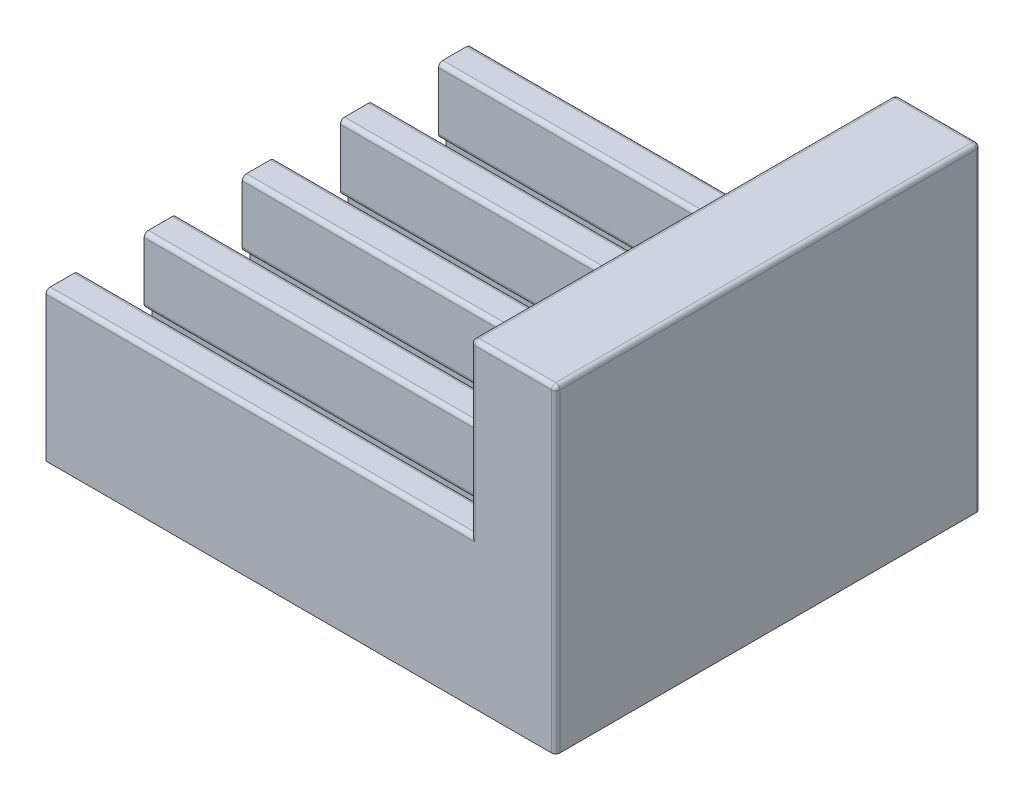
SolidWorks part; units mm, degrees
ref_plane "Front Plane" through (0, 0, 0) normal (0, 0, 1) x (1, 0, 0)
ref_plane "Top Plane" through (0, 0, 0) normal (0, 1, 0) x (1, 0, 0)
ref_plane "Right Plane" through (0, 0, 0) normal (1, 0, 0) x (0, 0, -1)
sketch "Sketch1" plane through (0, 0, 0) normal (0, 1, 0) x (1, 0, 0)
  line L1 (-63.5354, 42.4181) -> (56.4646, 42.4181)
  line L2 (-63.5354, 42.4181) -> (-63.5354, -57.5819)
  line L3 (-63.5354, -57.5819) -> (56.4646, -57.5819)
  line L4 (56.4646, 42.4181) -> (56.4646, -57.5819)
  dimension "D1" = 100
  dimension "D2" = 120
extrude "Boss-Extrude1" add sketch "Sketch1" along normal blind 75
sketch "Sketch2" plane through (0, 75, 0) normal (0, 1, 0) x (1, 0, 0)
  line L0 (-63.5354, -57.5819) -> (56.4646, -57.5819) construction
  line L1 (-63.5354, 42.4181) -> (36.4646, 42.4181)
  line L2 (-63.5354, 42.4181) -> (-63.5354, -57.5819)
  line L3 (-63.5354, -57.5819) -> (36.4646, -57.5819)
  line L4 (36.4646, 42.4181) -> (36.4646, -57.5819)
  dimension "D1" = 100
extrude "Cut-Extrude1" cut sketch "Sketch2" against normal blind 40
sketch "Sketch6" plane through (-63.5354, 0, 0) normal (-1, 0, 0) x (0, 0, 1)
  line L0 (57.5819, 35) -> (-42.4181, 35) construction
  line L1 (-34.8181, 35) -> (-19.3181, 35)
  line L2 (-34.8181, 35) -> (-34.8181, 19.5)
  line L3 (-34.8181, 19.5) -> (-19.3181, 19.5)
  line L4 (-19.3181, 35) -> (-19.3181, 19.5)
  line L5 (-19.3181, 27.25) -> (-11.7181, 27.25) construction
  line L6 (-11.7181, 35) -> (3.7819, 35)
  line L7 (-11.7181, 35) -> (-11.7181, 19.5)
  line L8 (-11.7181, 19.5) -> (3.7819, 19.5)
  line L9 (3.7819, 35) -> (3.7819, 19.5)
  line L10 (11.3819, 35) -> (26.8819, 35)
  line L11 (11.3819, 35) -> (11.3819, 19.5)
  line L12 (11.3819, 19.5) -> (26.8819, 19.5)
  line L13 (26.8819, 35) -> (26.8819, 19.5)
  line L14 (34.4819, 35) -> (49.9819, 35)
  line L15 (34.4819, 35) -> (34.4819, 19.5)
  line L16 (34.4819, 19.5) -> (49.9819, 19.5)
  line L17 (49.9819, 35) -> (49.9819, 19.5)
  line L18 (-15.5181, 27.25) -> (-15.5181, 0) construction
  line L19 (-42.4181, 0) -> (57.5819, 0) construction
  line L20 (7.5819, 35) -> (7.5819, 0) construction
  line L21 (-42.4181, 35) -> (57.5819, 35) construction
  circle A0 centre (-27.0681, 27.25) radius 5.95
  circle A1 centre (-3.9681, 27.25) radius 5.95
  circle A2 centre (42.2319, 27.25) radius 5.95
  circle A3 centre (19.1319, 27.25) radius 5.95
  dimension "D13" = 7.75
  dimension "D1" = 15.5
  dimension "D2" = 15.5
  dimension "D3" = 15.5
  dimension "D4" = 15.5
  dimension "D5" = 15.5
  dimension "D6" = 15.5
  dimension "D7" = 15.5
  dimension "D8" = 15.5
  dimension "D9" = 7.6
  dimension "D10" = 7.6
  dimension "D11" = 7.6
  dimension "D12" = 7.6
  dimension "D14" = 7.75
extrude "Cut-Extrude4" cut sketch "Sketch6" against normal blind 100 contours L11 L10 L13 L12 | L15 L14 L17 L16 | L7 L6 L9 L8 | L2 L1 L4 L3
sketch "Sketch8" plane through (-63.5354, 0, 0) normal (-1, 0, 0) x (0, 0, 1)
  line L1 (-36.6181, 19.5) -> (-17.5181, 19.5)
  line L2 (-36.6181, 19.5) -> (-36.6181, 9.5)
  line L3 (-36.6181, 9.5) -> (-17.5181, 9.5)
  line L4 (-17.5181, 19.5) -> (-17.5181, 9.5)
  line L6 (-15.5181, 35) -> (-15.5181, 0) construction
  line L7 (-19.3181, 35) -> (-11.7181, 35) construction
  line L8 (-42.4181, 0) -> (57.5819, 0) construction
  line L9 (5.5819, 9.5) -> (-13.5181, 9.5)
  line L10 (-13.5181, 19.5) -> (-13.5181, 9.5)
  line L11 (5.5819, 19.5) -> (-13.5181, 19.5)
  line L12 (5.5819, 19.5) -> (5.5819, 9.5)
  line L13 (7.5819, 35) -> (7.5819, 0) construction
  line L14 (11.3819, 35) -> (3.7819, 35) construction
  line L15 (51.7819, 9.5) -> (32.6819, 9.5)
  line L16 (32.6819, 19.5) -> (32.6819, 9.5)
  line L17 (51.7819, 19.5) -> (32.6819, 19.5)
  line L18 (51.7819, 19.5) -> (51.7819, 9.5)
  line L19 (9.5819, 19.5) -> (9.5819, 9.5)
  line L20 (9.5819, 19.5) -> (28.6819, 19.5)
  line L21 (28.6819, 19.5) -> (28.6819, 9.5)
  line L22 (9.5819, 9.5) -> (28.6819, 9.5)
  dimension "D1" = 1.8
  dimension "D2" = 10
  dimension "D3" = 19.1
extrude "Cut-Extrude5" cut sketch "Sketch8" against normal blind 100
extrude "Cut-Extrude6" cut sketch "Sketch6<3>" against normal blind 111 contours A0 | A1 | A3 | A2 region at (-63.5354, 27.25, -27.0681) region at (-63.5354, 27.25, -3.9681) region at (-63.5354, 27.25, 42.2319) region at (-63.5354, 27.25, 19.1319)
sketch "Sketch6<3>" plane through (-63.5354, 0, 0) normal (-1, 0, 0) x (0, 0, 1) same geometry as "Sketch6"
fillet "Fillet1" radius 1 10 edges at (-13.5354, 35, -42.4181) (-13.5354, 35, 57.5819) (36.4646, 55, -42.4181) (36.4646, 55, 57.5819) (46.4646, 75, 57.5819) (36.4646, 75, 7.5819) (46.4646, 75, -42.4181) (56.4646, 75, 7.5819) (56.4646, 37.5, 57.5819) (56.4646, 37.5, -42.4181)
chamfer "Chamfer1" distance 1 angle 45 4 edges at (36.4646, 27.25, 36.2819) (36.4646, 27.25, 13.1819) (36.4646, 27.25, -9.9181) (36.4646, 27.25, -33.0181)
fillet "Fillet2" radius 0.5 4 edges at (47.4646, 27.25, 48.1819) (47.4646, 27.25, 25.0819) (47.4646, 27.25, 1.9819) (47.4646, 27.25, -21.1181)
fillet "Fillet3" radius 1 16 edges at (-13.5354, 19.5, -19.3181) (-13.5354, 19.5, 3.7819) (-13.5354, 19.5, 26.8819) (-13.5354, 19.5, -34.8181) (-13.5354, 19.5, -11.7181) (-13.5354, 19.5, 11.3819) (-13.5354, 19.5, 34.4819) (-13.5354, 19.5, 49.9819) (-13.5354, 35, -34.8181) (-13.5354, 35, -19.3181) (-13.5354, 35, -11.7181) (-13.5354, 35, 3.7819) (-13.5354, 35, 26.8819) (-13.5354, 35, 11.3819) (-13.5354, 35, 34.4819) (-13.5354, 35, 49.9819)
